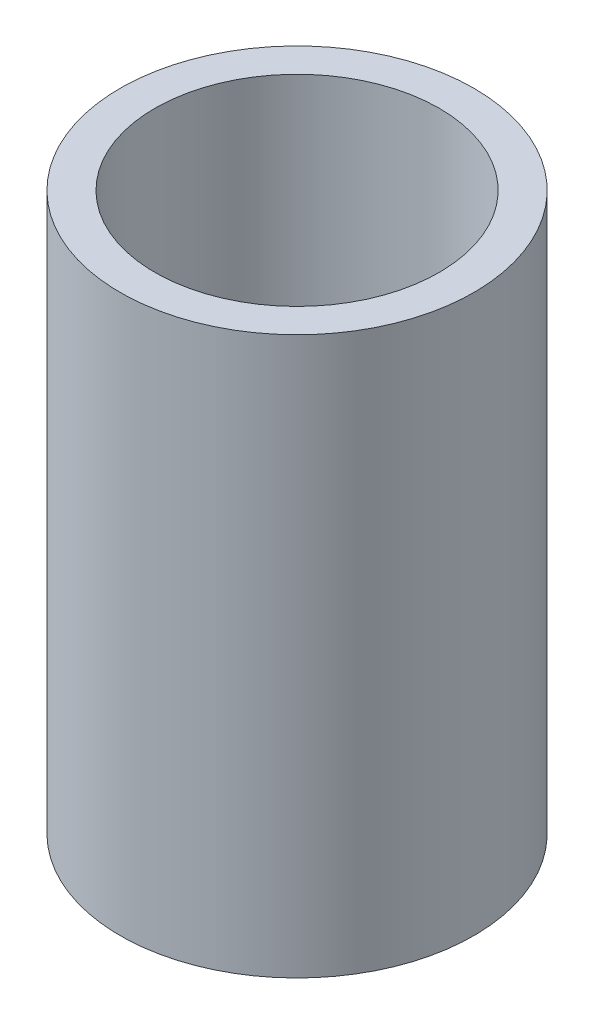
SolidWorks part; units mm, degrees
ref_plane "Front Plane" through (0, 0, 0) normal (0, 0, 1) x (1, 0, 0)
ref_plane "Top Plane" through (0, 0, 0) normal (0, 1, 0) x (1, 0, 0)
ref_plane "Right Plane" through (0, 0, 0) normal (1, 0, 0) x (0, 0, -1)
sketch "Sketch1" plane through (0, 70.8213, 0) normal (0, -1, 0) x (1, 0, 0)
  circle A0 centre (0, 0) radius 5.1054
  circle A1 centre (0, 0) radius 6.35
  dimension "D1" = 12.7
  dimension "D2" = 10.2108
extrude "Boss-Extrude1" add sketch "Sketch1" along normal blind 20
